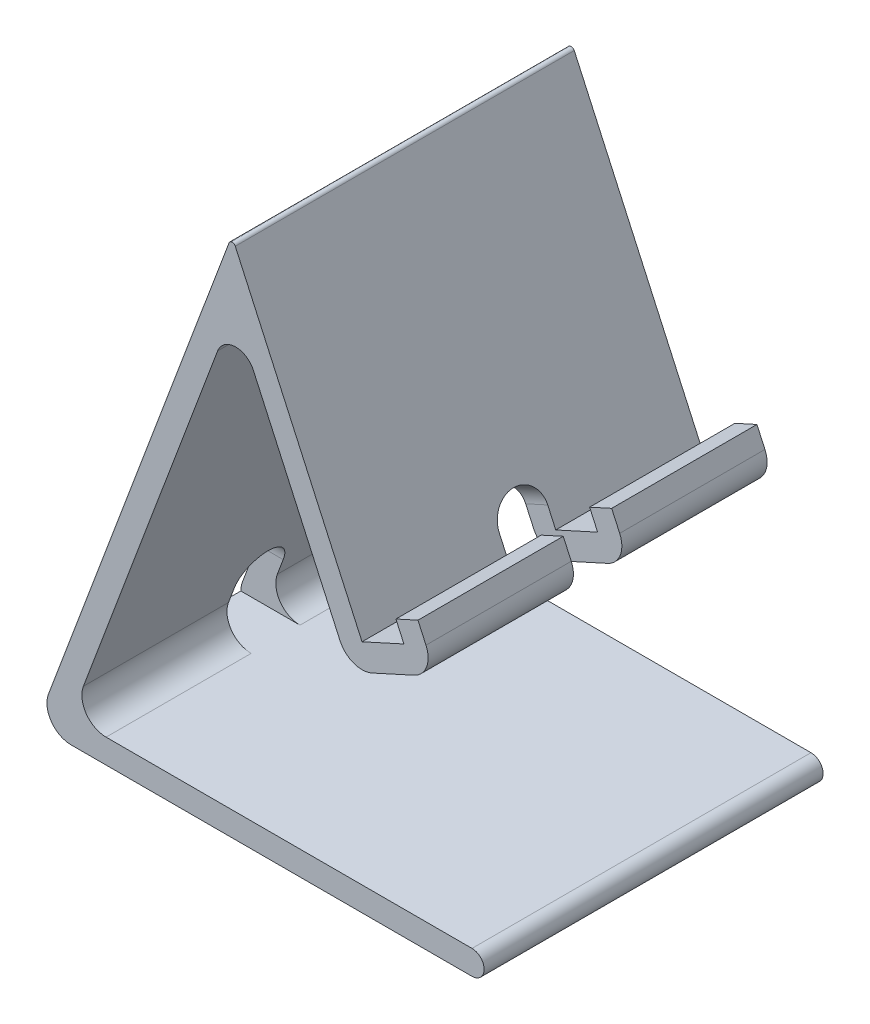
SolidWorks part; units mm, degrees
ref_plane "Front Plane" through (0, 0, 0) normal (0, 0, 1) x (1, 0, 0)
ref_plane "Top Plane" through (0, 0, 0) normal (0, 1, 0) x (1, 0, 0)
ref_plane "Right Plane" through (0, 0, 0) normal (1, 0, 0) x (0, 0, -1)
sketch "Sketch1" plane through (0, 0, 0) normal (0, 0, 1) x (1, 0, 0)
  line L0 (7.2176, 0) -> (90, 0)
  line L1 (2.5366, 6.7572) -> (39.8219, 106.082)
  line L2 (41.1146, 106.1254) -> (67.2929, 48.4812)
  line L3 (67.2929, 48.4812) -> (75.9427, 52.4094)
  line L4 (14.4352, 5) -> (90, 5)
  line L5 (9.7542, 11.7572) -> (37.4607, 85.565)
  line L6 (44.8476, 85.8132) -> (62.7403, 46.4137)
  line L8 (69.3603, 43.9286) -> (78.0101, 47.8568)
  line L9 (75.9427, 52.4094) -> (74.2887, 56.0514)
  line L10 (74.2887, 56.0514) -> (78.8412, 58.1189)
  line L12 (80.4952, 54.4768) -> (78.8412, 58.1189)
  line L13 (0, 0) -> (40.4158, 107.6641) construction
  line L14 (40.4158, 107.6641) -> (67.2929, 48.4812) construction
  line L15 (7.2176, 5) -> (40.8545, 94.6059) construction
  line L16 (40.8545, 94.6059) -> (62.7403, 46.4137) construction
  line L17 (7.2176, 5) -> (90, 5) construction
  line L18 (0, 0) -> (90, 0) construction
  arc A0 (90, 5) -> (90, 0) centre (90, 2.5) cw
  arc A1 (39.8219, 106.082) -> (41.1146, 106.1254) centre (40.4772, 105.836) cw
  arc A2 (37.4607, 85.565) -> (44.8476, 85.8132) centre (41.2056, 84.1593) cw
  arc A3 (69.3603, 43.9286) -> (62.7403, 46.4137) centre (67.2929, 48.4812) cw
  arc A4 (78.0101, 47.8568) -> (80.4952, 54.4768) centre (75.9427, 52.4094) ccw
  arc A5 (14.4352, 5) -> (9.7542, 11.7572) centre (14.4352, 10) cw
  arc A6 (7.2176, 0) -> (2.5366, 6.7572) centre (7.2176, 5) cw
  point P22 (40.4158, 107.6641)
  dimension "D10" = 0.7
  dimension "D11" = 4
  dimension "D7" = 5
  dimension "D12" = 5
  dimension "D13" = 5
  dimension "D3" = 65
  dimension "D4" = 45
  dimension "D5" = 9.5
  dimension "D8" = 4
  dimension "D9" = 5
  dimension "D6" = 5
sketch3d "3DSketch1" plane through (0, 0, 0) normal (0, 0, 1) x (1, 0, 0)
extrude "Boss-Extrude1" add sketch "Sketch1" along normal blind 70 contours L5 A2 L6 A3 L8 A4 L12 L10 L9 L3 L2 A1 L1 A6 L0 A0 L4 A5
sketch "Sketch3" plane through (74.04, 33.6242, 0) normal (0.9105, 0.4135, 0) x (0, 0, -1)
  line L0 (-35, 79.6273) -> (-35, 10.3173)
  line L1 (-70, 79.6273) -> (0, 79.6273) construction
  line L2 (-35, 10.3173) -> (-40, 10.3173)
  line L3 (-40, 10.3173) -> (-40, 20.3173)
  line L4 (-70, 20.3173) -> (0, 20.3173) construction
  line L5 (-30, 10.3173) -> (-30, 20.3173)
  line L6 (-40, 10.3173) -> (-30, 10.3173)
  arc A0 (-40, 20.3173) -> (-30, 20.3173) centre (-35, 20.3173) cw
  point P4 (-40, 15.3173)
  line M6 (-70, 16.3173) -> (0, 16.3173)
  dimension "D1" = 10
  dimension "D2" = 5
sketch "Sketch5" plane through (74.04, 33.6242, 0) normal (0.9105, 0.4135, 0) x (0, 0, -1)
extrude "Cut-Extrude1" cut sketch "Sketch3" against normal blind 40 and the other way blind 70 contours A0 L0 L5 M6 | L3 A0 L5 L6 region at (65.6215, 52.1615, 32.6872)
sketch "Sketch7" plane through (0, 0, 0) normal (1, 0, 0) x (0, 0, -1)
  line L0 (-35, 43.0181) -> (-35, 5)
  line L1 (-70, 5) -> (0, 5) construction
  line L2 (-29.9551, 5) -> (-40.0449, 5)
  line L3 (-40.0449, 5) -> (-40.0449, 14.9861)
  line L4 (-29.9551, 5) -> (-29.9551, 14.9861)
  arc A0 (-40.0449, 14.9861) -> (-29.9551, 14.9861) centre (-35, 14.9861) cw
extrude "Cut-Extrude2" cut sketch "Sketch7" along normal blind 122 contours L4 A0 L3 L2
